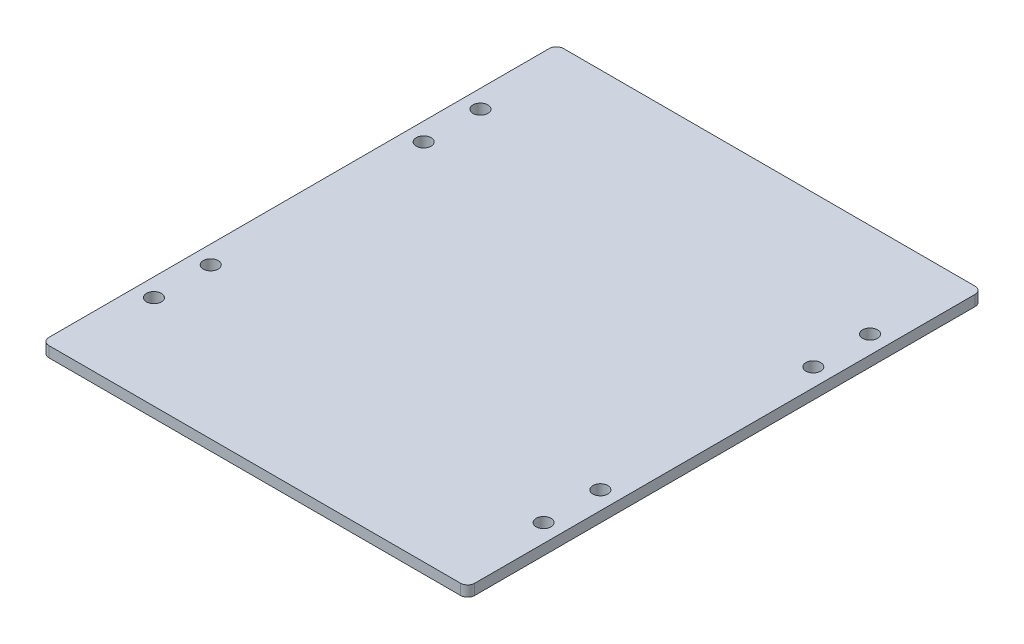
SolidWorks part; units mm, degrees
ref_plane "Front Plane" through (0, 0, 0) normal (0, 0, 1) x (1, 0, 0)
ref_plane "Top Plane" through (0, 0, 0) normal (0, 1, 0) x (1, 0, 0)
ref_plane "Right Plane" through (0, 0, 0) normal (1, 0, 0) x (0, 0, -1)
sketch "Sketch1" plane through (0, 0, 0) normal (0, 1, 0) x (1, 0, 0)
  line L0 (0, 145) -> (120, 0) construction
  line L1 (0, 0) -> (120, 0)
  line L2 (0, 0) -> (0, 145)
  line L3 (0, 145) -> (120, 145)
  line L4 (120, 0) -> (120, 145)
  dimension "length" = 145
  dimension "width" = 120
  dimension "D1" = 188.2153
extrude "Boss-Extrude1" add sketch "Sketch1" along normal blind 3
sketch "Sketch2" plane through (0, 3, 3) normal (0, 1, 0) x (1, 0, 0)
  line L0 (5.1, 105.5) -> (114.9, 105.5) construction
  line L5 (5.1, 121.5) -> (114.9, 121.5) construction
  line L6 (5.1, 121.5) -> (5.1, 29.5) construction
  line L7 (5.1, 29.5) -> (114.9, 29.5) construction
  line L8 (114.9, 121.5) -> (114.9, 29.5) construction
  line L9 (114.9, 45.5) -> (5.1, 45.5) construction
  line L16 (120, 148) -> (0, 148) construction
  line L17 (0, 148) -> (0, 3) construction
  circle A0 centre (5.1, 121.5) radius 2.1
  circle A1 centre (5.1, 105.5) radius 2.1
  circle A2 centre (5.1, 45.5) radius 2.1
  circle A3 centre (5.1, 29.5) radius 2.1
  circle A4 centre (114.9, 29.5) radius 2.1
  circle A5 centre (114.9, 45.5) radius 2.1
  circle A6 centre (114.9, 105.5) radius 2.1
  circle A7 centre (114.9, 121.5) radius 2.1
  point P2 (60, 148)
  point P3 (60, 121.5)
  point P15 (0, 75.5)
  point P16 (5.1, 75.5)
  dimension "D2" = 4.2
  dimension "D3" = 16
  dimension "D1" = 16
  dimension "D4" = 3
  dimension "D5" = 92
extrude "Cut-Extrude1" cut sketch "Sketch2" against normal through all
fillet "Fillet1" radius 2 4 edges at (0, 1.5, -145) (120, 1.5, -145) (120, 1.5, 0) (0, 1.5, 0)
equation "\"width\"= 24"
equation "\"thk\"= 3"
equation "\"holesize\"= 4.2"
equation "\"holedistance\"= ( 20 + 12 ) / 2"
equation "\"threaded_hole\"= 3.9"
equation "\"fillet_radius\"= 2"
equation "\"ground_clearance\"= 25"
equation "\"tire_thk\"= 4"
equation "\"innerwheel_diam\" = \"wheel_diam\"-2*\"tire_thk\""
equation "\"innerwheel_thk\"= 8"
equation "\"wheel_diam\"= 2*(\"width\"/2+\"ground_clearance\")"
equation "\"coloursensor_holesize\"= 2.65"
equation "\"D1@Boss-Extrude1\"=\"thk\""
equation "\"D3@Sketch2\"=\"holedistance\""
equation "\"D1@Sketch2\"=\"holedistance\""
equation "\"D2@Sketch2\"=\"holesize\""
equation "\"D1@Fillet1\"=\"fillet_radius\""
equation "\"D5@Sketch2\"=\"length@Sketch1\"-53"
